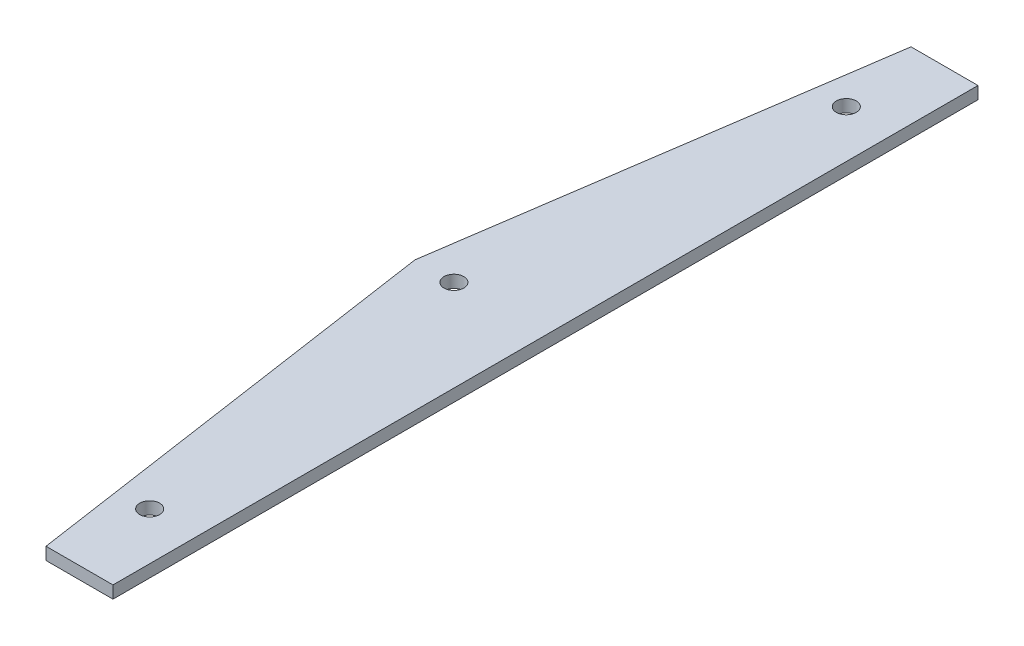
SolidWorks part; units mm, degrees
ref_plane "Front Plane" through (0, 0, 0) normal (0, 0, 1) x (1, 0, 0)
ref_plane "Top Plane" through (0, 0, 0) normal (0, 1, 0) x (1, 0, 0)
ref_plane "Right Plane" through (0, 0, 0) normal (1, 0, 0) x (0, 0, -1)
sketch "Sketch1" plane through (0, 7.6595, 0) normal (0, 1, 0) x (1, 0, 0)
  line L0 (-167.8237, -6.7743) -> (114.1763, -6.7743) construction
  line L1 (-141.5163, 104.251) -> (-124.3237, 104.251)
  line L3 (-141.5163, -117.7997) -> (-124.3237, -117.7997)
  line L4 (-124.3237, 104.251) -> (-124.3237, -117.7997)
  line L5 (-136.5163, 82.6365) -> (-136.5163, 125.8656) construction
  line L7 (-144.3237, 125.8656) -> (90.6763, 125.8656) construction
  line L8 (-141.5163, 104.251) -> (-157.8295, -6.7743)
  line L9 (-157.8295, -6.7743) -> (-141.5163, -117.7997)
  circle A0 centre (-147.8295, -6.7743) radius 2.5527 construction
  circle A1 centre (-136.5163, -96.1851) radius 2.5527 construction
  circle A2 centre (-136.5163, 82.6365) radius 2.5527 construction
  circle A3 centre (-136.5163, -96.1851) radius 2.5527
  circle A4 centre (-147.8295, -6.7743) radius 2.5527
  circle A5 centre (-136.5163, 82.6365) radius 2.5527
  point P8 (-136.5163, 104.251)
  point P10 (-124.3237, -6.7743)
  dimension "D1" = 10
extrude "MainBody" add sketch "Sketch1" against normal blind 3.175
